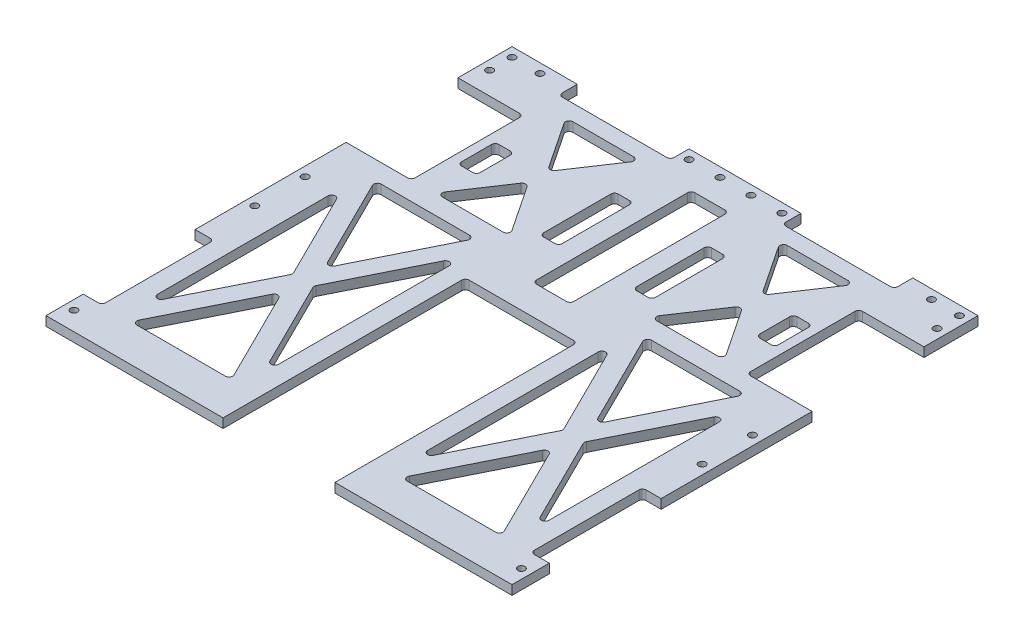
SolidWorks part; units mm, degrees
material "7050-T73510"
ref_plane "Front Plane" through (0, 0, 0) normal (0, 0, 1) x (1, 0, 0)
ref_plane "Top Plane" through (0, 0, 0) normal (0, 1, 0) x (1, 0, 0)
ref_plane "Right Plane" through (0, 0, 0) normal (1, 0, 0) x (0, 0, -1)
sketch "Sketch1" plane through (0, 0, 0) normal (0, 1, 0) x (1, 0, 0)
  line L0 (0, -55) -> (0, 55) construction
  line L1 (-158.75, -76.2) -> (158.75, -76.2)
  line L2 (-158.75, -76.2) -> (-158.75, 76.2)
  line L3 (-158.75, 76.2) -> (158.75, 76.2)
  line L4 (158.75, -76.2) -> (158.75, 76.2)
  line L5 (-158.75, -76.2) -> (158.75, 76.2) construction
  line L6 (-158.75, 76.2) -> (158.75, -76.2) construction
  line L7 (-158.75, -76.2) -> (-25.4, -76.2)
  line L8 (-158.75, -76.2) -> (-158.75, -241.3)
  line L9 (-158.75, -241.3) -> (-25.4, -241.3)
  line L10 (-25.4, -76.2) -> (-25.4, -241.3)
  line L11 (25.4, -76.2) -> (25.4, -241.3)
  line L12 (158.75, -241.3) -> (25.4, -241.3)
  line L13 (158.75, -76.2) -> (158.75, -241.3)
  line L14 (158.75, -76.2) -> (25.4, -76.2)
  line L15 (-38.1, -76.2) -> (-38.1, -241.3)
  line L16 (38.1, -76.2) -> (38.1, -241.3)
  point P0 (0, 0)
  dimension "D1" = 317.5
  dimension "D2" = 152.4
  dimension "D3" = 317.5
  dimension "D4" = 50.8
  dimension "D5" = 12.7
extrude "Boss-Extrude1" add sketch "Sketch1" along normal blind 6.35 contours L15 L1 L8 L9 | L14 L16 L12 L13 | L1 L7 L14 L4 L3 L2 region at (0, 0, 0) region at (-98.425, 0, 158.75) region at (98.425, 0, 158.75)
sketch "Sketch2" plane through (0, 6.35, 0) normal (0, 1, 0) x (1, 0, 0)
  line L0 (158.75, -241.3) -> (158.75, 76.2) construction
  line L1 (158.75, 39.37) -> (114.3, 39.37)
  line L2 (158.75, 39.37) -> (158.75, -36.83)
  line L3 (158.75, -36.83) -> (114.3, -36.83)
  line L4 (114.3, 39.37) -> (114.3, -36.83)
  line L5 (-158.75, 76.2) -> (158.75, 76.2) construction
  line L6 (158.75, -139.7) -> (146.05, -139.7)
  line L7 (158.75, -139.7) -> (158.75, -215.9)
  line L8 (158.75, -215.9) -> (146.05, -215.9)
  line L9 (146.05, -139.7) -> (146.05, -215.9)
  line L10 (0, -55) -> (0, 55) construction
  line L11 (-158.75, -215.9) -> (-146.05, -215.9)
  line L12 (-146.05, -139.7) -> (-146.05, -215.9)
  line L13 (-158.75, -139.7) -> (-146.05, -139.7)
  line L14 (-158.75, -139.7) -> (-158.75, -215.9)
  line L15 (-158.75, -36.83) -> (-114.3, -36.83)
  line L16 (-114.3, 39.37) -> (-114.3, -36.83)
  line L17 (-158.75, 39.37) -> (-114.3, 39.37)
  line L18 (-158.75, 39.37) -> (-158.75, -36.83)
  line L19 (-114.3, 63.5) -> (-38.1, 63.5)
  line L20 (114.3, 76.2) -> (38.1, 76.2)
  line L21 (114.3, 76.2) -> (114.3, 63.5)
  line L22 (114.3, 63.5) -> (38.1, 63.5)
  line L23 (38.1, 76.2) -> (38.1, 63.5)
  line L24 (-38.1, 76.2) -> (-38.1, 63.5)
  line L25 (-114.3, 76.2) -> (-38.1, 76.2)
  line L26 (-114.3, 76.2) -> (-114.3, 63.5)
  dimension "D1" = 44.45
  dimension "D2" = 12.7
  dimension "D3" = 76.2
  dimension "D4" = 76.2
  dimension "D5" = 36.83
  dimension "D6" = 215.9
  dimension "D7" = 76.2
  dimension "D8" = 12.7
  dimension "D9" = 76.2
extrude "Cut-Extrude1" cut sketch "Sketch2" against normal through all
sketch "Sketch4" plane through (0, 6.35, 0) normal (0, 1, 0) x (1, 0, 0)
  line L0 (38.1, -76.2) -> (38.1, -241.3) construction
  line L1 (50.8, -215.9) -> (133.35, -215.9)
  line L2 (50.8, -215.9) -> (50.8, -49.53)
  line L3 (50.8, -49.53) -> (133.35, -49.53)
  line L4 (133.35, -215.9) -> (133.35, -49.53)
  line L5 (146.05, -139.7) -> (146.05, -215.9) construction
  line L6 (158.75, -241.3) -> (38.1, -241.3) construction
  line L7 (50.8, -215.9) -> (133.35, -49.53) construction
  line L8 (50.8, -49.53) -> (133.35, -215.9) construction
  line L9 (133.35, -201.6135) -> (57.8887, -49.53)
  line L10 (126.2613, -215.9) -> (50.8, -63.8165)
  line L11 (50.8, -201.6135) -> (126.2613, -49.53)
  line L12 (57.8887, -215.9) -> (133.35, -63.8165)
  line L13 (114.3, -36.83) -> (158.75, -36.83) construction
  line L14 (0, -55) -> (0, 55) construction
  line L15 (-50.8, -201.6135) -> (-126.2613, -49.53)
  line L16 (-126.2613, -215.9) -> (-50.8, -63.8165)
  line L17 (-133.35, -201.6135) -> (-57.8887, -49.53)
  line L18 (-57.8887, -215.9) -> (-133.35, -63.8165)
  line L19 (-50.8, -49.53) -> (-133.35, -49.53)
  line L20 (-133.35, -215.9) -> (-133.35, -49.53)
  line L21 (-50.8, -215.9) -> (-133.35, -215.9)
  line L22 (-50.8, -215.9) -> (-50.8, -49.53)
  point P18 (116.2026, -167.0549)
  dimension "D1" = 12.7
  dimension "D2" = 12.7
  dimension "D3" = 25.4
  dimension "D4" = 12.7
  dimension "D5" = 12.7
extrude "Cut-Extrude3" cut sketch "Sketch4" against normal through all contours L12 L9 L4 | L12 L1 L10 | L2 L11 L10 | L9 L11 L3 | L21 L18 L16 | L20 L17 L18 | L17 L19 L15 | L15 L22 L16 region at (92.075, 6.35, 192.9338) region at (62.1954, 6.35, 132.715) region at (121.9546, 6.35, 132.715) region at (92.075, 6.35, 72.4962) region at (-62.1954, 6.35, 132.715) region at (-92.075, 6.35, 72.4962) region at (-92.075, 6.35, 192.9338) region at (-121.9546, 6.35, 132.715)
sketch "Sketch3" plane through (0, 6.35, 0) normal (0, 1, 0) x (1, 0, 0)
  line L0 (-38.1, -76.2) -> (38.1, -76.2) construction
  line L1 (-38.1, -25.4) -> (-25.4, -25.4)
  line L2 (-38.1, -25.4) -> (-38.1, 25.4)
  line L3 (-38.1, 25.4) -> (-25.4, 25.4)
  line L4 (-25.4, -25.4) -> (-25.4, 25.4)
  line L5 (0, -55) -> (0, 55) construction
  line L6 (38.1, 25.4) -> (25.4, 25.4)
  line L7 (25.4, -25.4) -> (25.4, 25.4)
  line L8 (38.1, -25.4) -> (25.4, -25.4)
  line L9 (38.1, -25.4) -> (38.1, 25.4)
  line L10 (114.3, 39.37) -> (114.3, -36.83) construction
  line L11 (95.25, 13.97) -> (107.95, 13.97)
  line L12 (95.25, 13.97) -> (95.25, -11.43)
  line L13 (95.25, -11.43) -> (107.95, -11.43)
  line L14 (107.95, 13.97) -> (107.95, -11.43)
  line L15 (38.1, 63.5) -> (114.3, 63.5) construction
  line L16 (-95.25, -11.43) -> (-107.95, -11.43)
  line L17 (-107.95, 13.97) -> (-107.95, -11.43)
  line L18 (-95.25, 13.97) -> (-107.95, 13.97)
  line L19 (-95.25, 13.97) -> (-95.25, -11.43)
  dimension "D1" = 50.8
  dimension "D2" = 12.7
  dimension "D3" = 50.8
  dimension "D4" = 50.8
  dimension "D5" = 25.4
  dimension "D6" = 12.7
  dimension "D7" = 6.35
  dimension "D8" = 49.53
extrude "Cut-Extrude2" cut sketch "Sketch3" against normal through all
sketch "Sketch7" plane through (0, 6.35, 0) normal (0, 1, 0) x (1, 0, 0)
  line L0 (158.75, -139.7) -> (146.05, -139.7) construction
  line L1 (158.75, -139.7) -> (158.75, -36.83) construction
  line L2 (0, -55) -> (0, 55) construction
  line L3 (158.75, -241.3) -> (38.1, -241.3) construction
  line L4 (-38.1, 76.2) -> (-38.1, 63.5) construction
  line L5 (114.3, 76.2) -> (158.75, 76.2) construction
  line L6 (-38.1, 76.2) -> (38.1, 76.2) construction
  circle A0 centre (152.4, -105.41) radius 2.413
  circle A1 centre (152.4, -71.12) radius 2.413
  circle A8 centre (152.4, -228.6) radius 2.413
  circle A9 centre (152.4, 69.85) radius 2.413
  circle A10 centre (133.35, 69.85) radius 2.413
  circle A12 centre (152.4, 54.61) radius 2.413
  circle A19 centre (-152.4, -228.6) radius 2.413
  circle A20 centre (-31.75, 69.85) radius 2.413
  circle A21 centre (-10.668, 69.85) radius 2.413
  circle A22 centre (10.414, 69.85) radius 2.413
  circle A23 centre (31.496, 69.85) radius 2.413
  circle A24 centre (-152.4, 54.61) radius 2.413
  circle A25 centre (-133.35, 69.85) radius 2.413
  circle A26 centre (-152.4, 69.85) radius 2.413
  circle A27 centre (-152.4, -71.12) radius 2.413
  circle A28 centre (-152.4, -105.41) radius 2.413
  dimension "D1" = 4.826
  dimension "D3" = 6.35
  dimension "D5" = 12.7
  dimension "D6" = 6.35
  dimension "D9" = 4.826
  dimension "D2" = 34.29
  dimension "D8" = 2
  dimension "D10" = 6.35
  dimension "D11" = 6.35
  dimension "D4" = 2
  dimension "D7" = 2
  dimension "D12" = 4
extrude "Cut-Extrude6" cut sketch "Sketch7" against normal through all
sketch "Sketch12" plane through (0, 6.35, 0) normal (0, 1, 0) x (1, 0, 0)
  line L0 (-98.425, 52.6142) -> (-47.625, 52.6142)
  line L1 (-47.625, 52.6142) -> (-73.025, 14.5142)
  line L2 (-73.025, 14.5142) -> (-98.425, 52.6142)
  line L3 (-94.4842, 8.1642) -> (-61.9728, 8.1642) construction
  line L4 (-114.3, 39.37) -> (-114.3, -36.83) construction
  line L5 (-47.625, -36.2858) -> (-73.025, 1.8142)
  line L6 (-98.425, -36.2858) -> (-47.625, -36.2858)
  line L7 (-73.025, 1.8142) -> (-98.425, -36.2858)
  line L8 (0, -55) -> (0, 55) construction
  line L9 (94.4842, 8.1642) -> (61.9728, 8.1642) construction
  line L10 (73.025, 1.8142) -> (98.425, -36.2858)
  line L11 (98.425, -36.2858) -> (47.625, -36.2858)
  line L12 (47.625, -36.2858) -> (73.025, 1.8142)
  line L13 (73.025, 14.5142) -> (98.425, 52.6142)
  line L14 (47.625, 52.6142) -> (73.025, 14.5142)
  line L15 (98.425, 52.6142) -> (47.625, 52.6142)
  line L23 (-12.7, -55.6542) -> (12.7, -55.6542)
  line L24 (-12.7, -55.6542) -> (-12.7, 52.2958)
  line L25 (-12.7, 52.2958) -> (12.7, 52.2958)
  line L26 (12.7, -55.6542) -> (12.7, 52.2958)
  point P6 (-73.025, 52.6142)
  point P25 (0, -55.6542)
  dimension "D1" = 6.35
  dimension "D2" = 44.45
  dimension "D3" = 50.8
  dimension "D4" = 41.275
  dimension "D5" = 25.4
  dimension "D6" = 107.95
extrude "Cut-Extrude9" cut sketch "Sketch12" against normal through all
fillet "Fillet1" radius 2.54 20 edges at (-12.7, 3.175, 55.6542) (-12.7, 3.175, -52.2958) (-133.35, 3.175, 63.8165) (-133.35, 3.175, 201.6135) (-126.2613, 3.175, 215.9) (-57.8887, 3.175, 215.9) (-92.075, 3.175, 147.0015) (-84.9863, 3.175, 132.715) (-50.8, 3.175, 63.8165) (-50.8, 3.175, 201.6135) (-92.075, 3.175, 118.4285) (-99.1637, 3.175, 132.715) (-57.8887, 3.175, 49.53) (-126.2613, 3.175, 49.53) (-98.425, 3.175, 36.2858) (-47.625, 3.175, 36.2858) (-73.025, 3.175, -1.8142) (-73.025, 3.175, -14.5142) (-47.625, 3.175, -52.6142) (-98.425, 3.175, -52.6142)
fillet "Fillet2" radius 2.54 20 edges at (50.8, 3.175, 63.8165) (133.35, 3.175, 63.8165) (92.075, 3.175, 147.0015) (99.1637, 3.175, 132.715) (50.8, 3.175, 201.6135) (57.8887, 3.175, 215.9) (133.35, 3.175, 201.6135) (84.9863, 3.175, 132.715) (126.2613, 3.175, 215.9) (92.075, 3.175, 118.4285) (57.8887, 3.175, 49.53) (126.2613, 3.175, 49.53) (73.025, 3.175, -1.8142) (47.625, 3.175, 36.2858) (98.425, 3.175, 36.2858) (98.425, 3.175, -52.6142) (73.025, 3.175, -14.5142) (12.7, 3.175, 55.6542) (12.7, 3.175, -52.2958) (47.625, 3.175, -52.6142)
fillet "Fillet3" radius 2.54 30 edges at (-107.95, 3.175, 11.43) (-95.25, 3.175, 11.43) (-95.25, 3.175, -13.97) (-107.95, 3.175, -13.97) (95.25, 3.175, 11.43) (107.95, 3.175, 11.43) (107.95, 3.175, -13.97) (95.25, 3.175, -13.97) (114.3, 3.175, -63.5) (38.1, 3.175, -63.5) (-38.1, 3.175, -63.5) (-114.3, 3.175, -63.5) (146.05, 3.175, 215.9) (146.05, 3.175, 139.7) (-146.05, 3.175, 215.9) (-146.05, 3.175, 139.7) (38.1, 3.175, 76.2) (-38.1, 3.175, 76.2) (-114.3, 3.175, 36.83) (-114.3, 3.175, -39.37) (114.3, 3.175, -39.37) (114.3, 3.175, 36.83) (-25.4, 3.175, 25.4) (-38.1, 3.175, 25.4) (-38.1, 3.175, -25.4) (-25.4, 3.175, -25.4) (25.4, 3.175, 25.4) (38.1, 3.175, 25.4) (38.1, 3.175, -25.4) (25.4, 3.175, -25.4)
